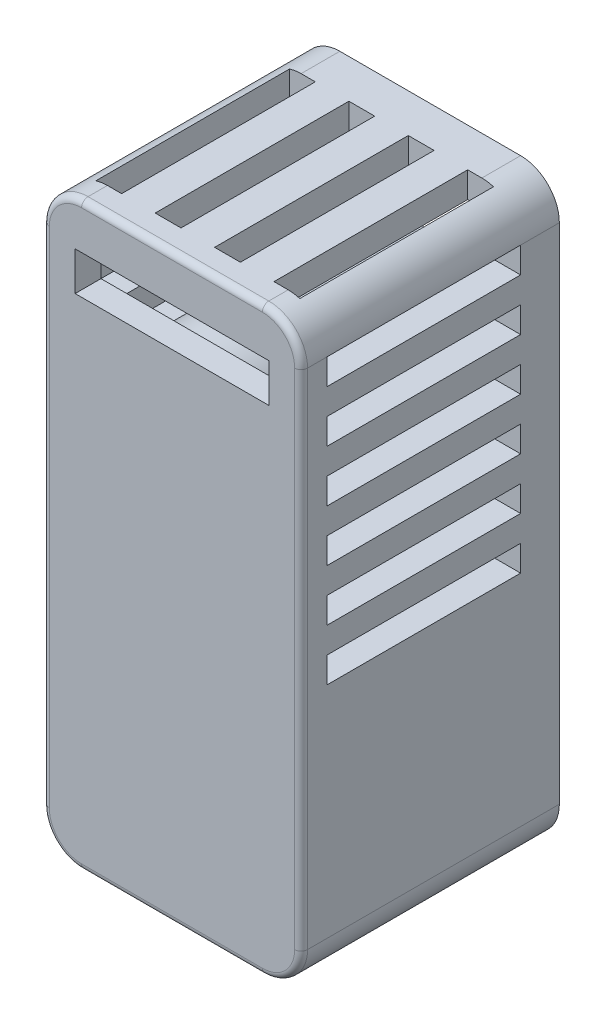
SolidWorks part; units mm, degrees
ref_plane "Front Plane" through (0, 0, 0) normal (0, 0, 1) x (1, 0, 0)
ref_plane "Top Plane" through (0, 0, 0) normal (0, 1, 0) x (1, 0, 0)
ref_plane "Right Plane" through (0, 0, 0) normal (1, 0, 0) x (0, 0, -1)
sketch "Sketch2" plane through (0, 0, 0) normal (0, 0, 1) x (1, 0, 0)
  line L1 (10, -22.5) -> (-10, -22.5)
  line L2 (10, -22.5) -> (10, 22.5)
  line L3 (10, 22.5) -> (-10, 22.5)
  line L4 (-10, -22.5) -> (-10, 22.5)
  line L5 (10, -22.5) -> (-10, 22.5) construction
  line L6 (10, 22.5) -> (-10, -22.5) construction
  point P0 (0, 0)
  dimension "D1" = 20
  dimension "D2" = 45
extrude "Boss-Extrude1" add sketch "Sketch2" along normal blind 20
shell "Shell1" thickness 2 removed face at (0, 0, 0)
sketch "Sketch3" plane through (10, 0, 0) normal (1, 0, 0) x (0, 0, -1)
  line L0 (-20, 22.5) -> (0, 22.5) construction
  line L1 (-18, 19.5) -> (-3, 19.5)
  line L2 (-18, 19.5) -> (-18, 17.5)
  line L3 (-18, 17.5) -> (-3, 17.5)
  line L4 (-3, 19.5) -> (-3, 17.5)
  line L5 (-20, -22.5) -> (-20, 22.5) construction
  line L6 (0, 55) -> (0, -55) construction
  line L7 (-18, 15.5) -> (-3, 15.5)
  line L8 (-18, 15.5) -> (-18, 13.5)
  line L9 (-18, 13.5) -> (-3, 13.5)
  line L10 (-3, 15.5) -> (-3, 13.5)
  line L11 (-18, 11.5) -> (-3, 11.5)
  line L12 (-18, 11.5) -> (-18, 9.5)
  line L13 (-18, 9.5) -> (-3, 9.5)
  line L14 (-3, 11.5) -> (-3, 9.5)
  line L15 (-18, 7.5) -> (-3, 7.5)
  line L16 (-18, 7.5) -> (-18, 5.5)
  line L17 (-18, 5.5) -> (-3, 5.5)
  line L18 (-3, 7.5) -> (-3, 5.5)
  line L19 (-18, 3.5) -> (-3, 3.5)
  line L20 (-18, 3.5) -> (-18, 1.5)
  line L21 (-18, 1.5) -> (-3, 1.5)
  line L22 (-3, 3.5) -> (-3, 1.5)
  line L23 (-18, -0.5) -> (-3, -0.5)
  line L24 (-18, -0.5) -> (-18, -2.5)
  line L25 (-18, -2.5) -> (-3, -2.5)
  line L26 (-3, -0.5) -> (-3, -2.5)
  dimension "D1" = 3
  dimension "D2" = 2
  dimension "D3" = 3
  dimension "D4" = 2
  dimension "D5" = 6
extrude "Cut-Extrude1" cut sketch "Sketch3" against normal up to surface (20 mm away) up to face at (-10, 0, 10)
sketch "Sketch4" plane through (0, 22.5, 0) normal (0, 1, 0) x (1, 0, 0)
  line L0 (10, -20) -> (-10, -20) construction
  line L1 (-7.9, -3) -> (-5.9, -3)
  line L2 (-7.9, -3) -> (-7.9, -18)
  line L3 (-7.9, -18) -> (-5.9, -18)
  line L4 (-5.9, -3) -> (-5.9, -18)
  line L5 (-55, 0) -> (55, 0) construction
  line L6 (-3.3, -3) -> (-1.3, -3)
  line L7 (-3.3, -3) -> (-3.3, -18)
  line L8 (-3.3, -18) -> (-1.3, -18)
  line L9 (-1.3, -3) -> (-1.3, -18)
  line L10 (1.3, -3) -> (3.3, -3)
  line L11 (1.3, -3) -> (1.3, -18)
  line L12 (1.3, -18) -> (3.3, -18)
  line L13 (3.3, -3) -> (3.3, -18)
  line L14 (5.9, -3) -> (7.9, -3)
  line L15 (5.9, -3) -> (5.9, -18)
  line L16 (5.9, -18) -> (7.9, -18)
  line L17 (7.9, -3) -> (7.9, -18)
  line L18 (-10, -20) -> (-10, 0) construction
  dimension "D1" = 2
  dimension "D2" = 3
  dimension "D3" = 2
  dimension "D5" = 2.1
  dimension "D4" = 4
extrude "Cut-Extrude2" cut sketch "Sketch4" against normal up to next
fillet "Fillet1" radius 3 4 edges at (10, -22.5, 10) (-10, -22.5, 10) (-10, 22.5, 10) (10, 22.5, 10)
sketch "Sketch7" plane through (0, 0, 20) normal (0, 0, 1) x (1, 0, 0)
  line L5 (0, -11) -> (0, 11) construction
  line L6 (7.5, 16) -> (-7.5, 16)
  line L10 (7.5, 16) -> (7.5, 19)
  line L11 (7.5, 19) -> (-7.5, 19)
  line L16 (-7.5, 16) -> (-7.5, 19)
  line L17 (7.5, 16) -> (-7.5, 19) construction
  line L30 (7.5, 19) -> (-7.5, 16) construction
  line L31 (7, 22.5) -> (-7, 22.5) construction
  point P0 (0, 17.5)
  point P5 (0, 12.9508)
  point P6 (0, 10.4378)
  point P8 (0, 0)
  point P9 (0, 0)
  dimension "D1" = 3
  dimension "D2" = 15
  dimension "D3" = 5
extrude "Cut-Extrude3" cut sketch "Sketch7" against normal up to surface (2 mm away) up to face at (0, 11.3827, 18)
fillet "Fillet3" radius 0.5 8 edges at (9.1213, 21.6213, 20) (0, 22.5, 20) (-9.1213, 21.6213, 20) (-10, 0, 20) (-9.1213, -21.6213, 20) (0, -22.5, 20) (9.1213, -21.6213, 20) (10, 0, 20)
sketch "Sketch8" plane through (0, 0, 18) normal (0, 0, -1) x (-1, 0, 0)
  line L0 (-8, 20.5) -> (8, 20.5) construction
  circle A0 centre (0, 10.5) radius 2.8
  circle A1 centre (0, 10.5) radius 5.2
  dimension "D1" = 2.4
  dimension "D2" = 10
extrude "Boss-Extrude2" add sketch "Sketch8" along normal blind 16.4
